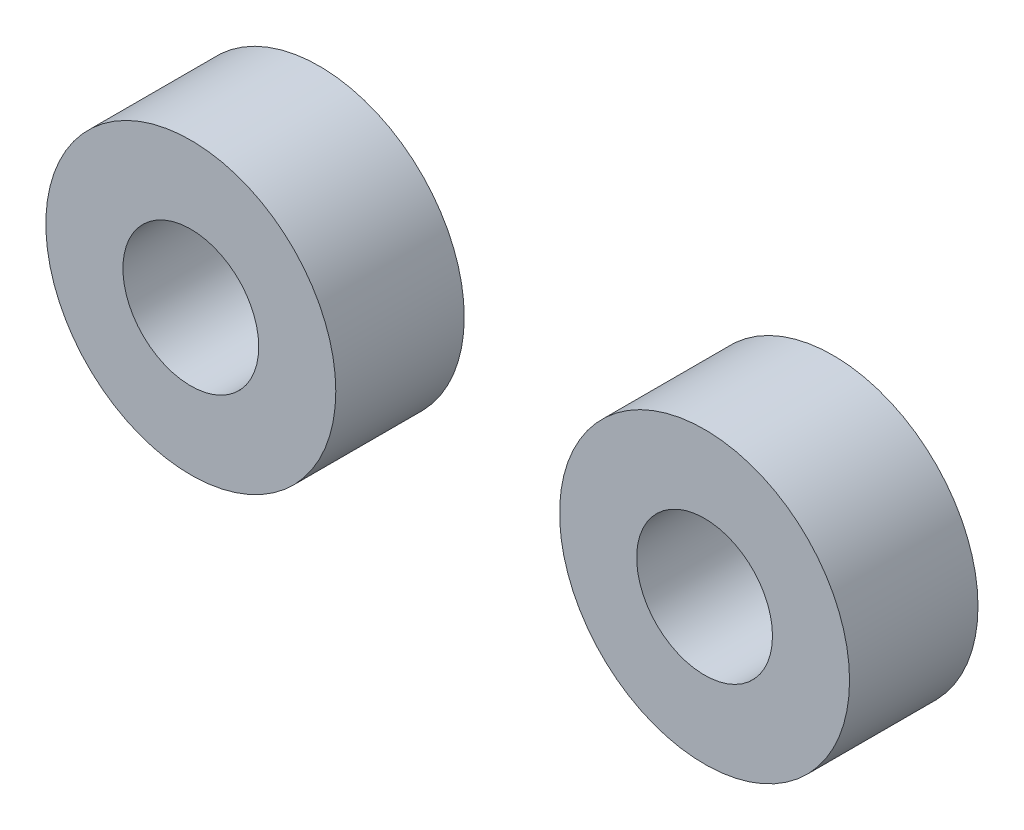
SolidWorks part; units mm, degrees
ref_plane "前视基准面" through (0, 0, 0) normal (0, 0, 1) x (1, 0, 0)
ref_plane "上视基准面" through (0, 0, 0) normal (0, 1, 0) x (1, 0, 0)
ref_plane "右视基准面" through (0, 0, 0) normal (1, 0, 0) x (0, 0, -1)
other "Configuration Table"
sketch "草图1" plane through (0, 0, 0) normal (0, 0, 1) x (1, 0, 0)
  line L0 (-65.5685, 14.6408) -> (-13.9253, 14.6408) construction
  circle A0 centre (-49.9595, 14.3913) radius 5.6436
  circle A1 centre (-29.961, 14.6408) radius 5.6436
  circle A2 centre (-49.9595, 14.3913) radius 2.6436
  circle A3 centre (-29.961, 14.6408) radius 2.6436
  dimension "D1" = 20
  dimension "D2" = 3
  dimension "D3" = 3
extrude "凸台-拉伸1" add sketch "草图1" along normal blind 5
extrude "凸台-拉伸2" add sketch "草图1<2>" along normal blind 5
sketch "草图1<2>" plane through (0, 0, 0) normal (0, 0, 1) x (1, 0, 0) same geometry as "草图1"
